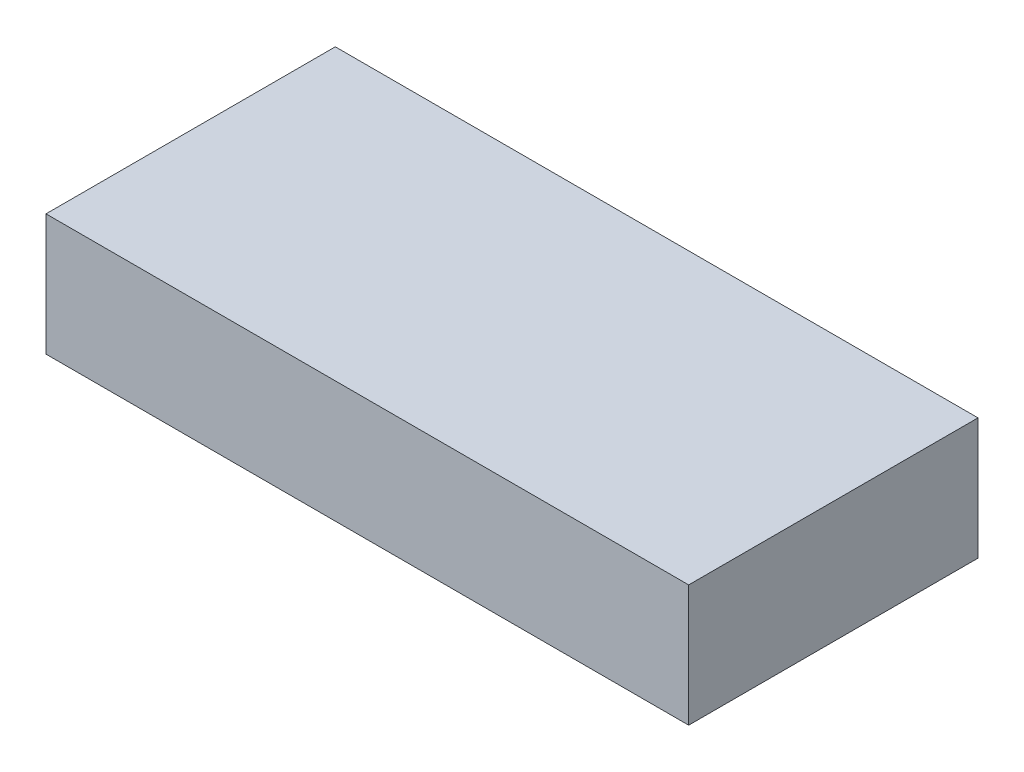
SolidWorks part; units mm, degrees
ref_plane "Front Plane" through (0, 0, 0) normal (0, 0, 1) x (1, 0, 0)
ref_plane "Top Plane" through (0, 0, 0) normal (0, 1, 0) x (1, 0, 0)
ref_plane "Right Plane" through (0, 0, 0) normal (1, 0, 0) x (0, 0, -1)
sketch "Sketch2" plane through (0, 0, 0) normal (0, 0, 1) x (1, 0, 0)
  line L0 (11.1072, -2.1) -> (-11.1072, -2.1)
  line L1 (-11.1072, -2.1) -> (-11.1072, 2.1)
  line L2 (-11.1072, 2.1) -> (11.1072, 2.1)
  line L3 (11.1072, 2.1) -> (11.1072, -2.1)
extrude "Boss-Extrude1" add sketch "Sketch2" along normal blind 10
